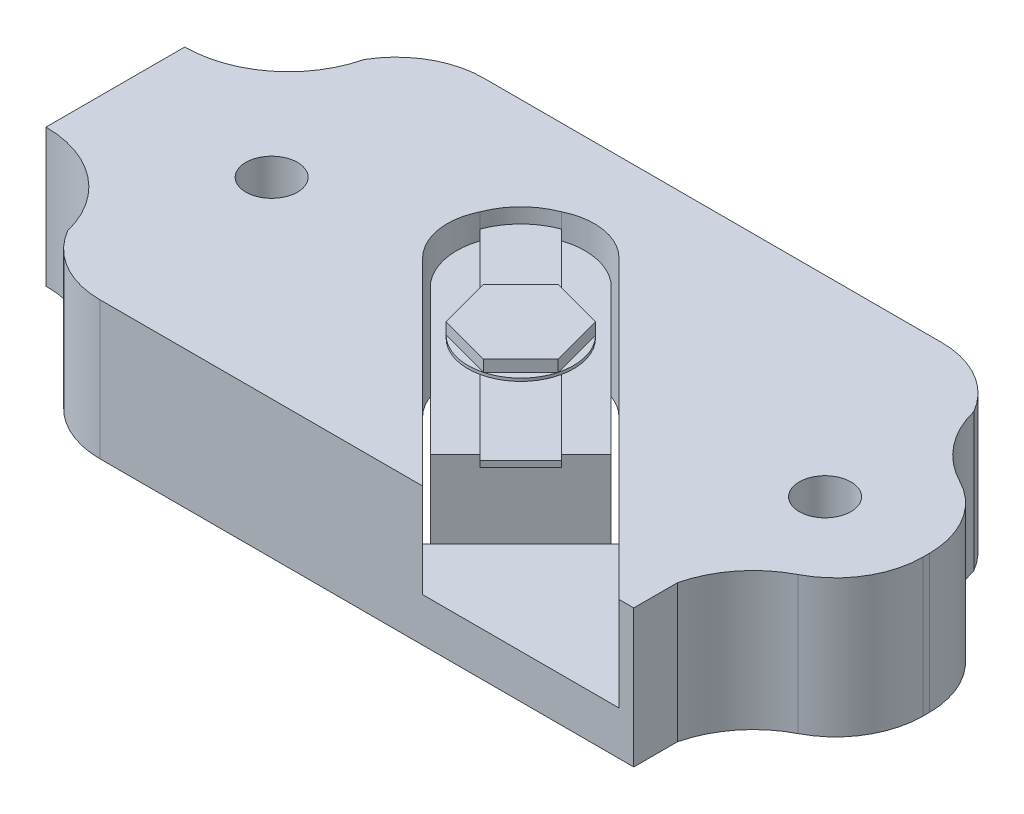
SolidWorks part; units mm, degrees
ref_plane "Front Plane" through (0, 0, 0) normal (0, 0, 1) x (1, 0, 0)
ref_plane "Top Plane" through (0, 0, 0) normal (0, 1, 0) x (1, 0, 0)
ref_plane "Right Plane" through (0, 0, 0) normal (1, 0, 0) x (0, 0, -1)
sketch "Sketch4" plane through (0, 0, 0) normal (0, 1, 0) x (1, 0, 0)
  line L0 (-37.15, 0) -> (37.15, 0) construction
  line L1 (37.15, 0) -> (28.55, 0) construction
  line L2 (37.15, 0) -> (-19.65, 0) construction
  circle A0 centre (-21.7, 0) radius 2.05
  circle A1 centre (26.5, 0) radius 2.05
  point P4 (0, 0)
  dimension "D4" = 4.1
  dimension "D5" = 4.1
  dimension "D6" = 2.05
  dimension "D1" = 74.3
  dimension "D2" = 8.6
  dimension "D3" = 56.8
sketch "Sketch1" plane through (0, 0, 0) normal (0, 1, 0) x (1, 0, 0)
  line L0 (-8.2731, 8.2731) -> (-4.7376, 4.7376) construction
  line L1 (-12.1976, 4.3487) -> (4.3487, -12.1976)
  line L2 (-12.1976, 4.3487) -> (-4.3487, 12.1976)
  line L3 (-4.3487, 12.1976) -> (12.1976, -4.3487)
  line L4 (4.3487, -12.1976) -> (12.1976, -4.3487)
  line L5 (-12.1976, 4.3487) -> (12.1976, -4.3487) construction
  line L6 (-4.3487, 12.1976) -> (4.3487, -12.1976) construction
  line L7 (-8.6621, 0.8132) -> (-0.8132, 8.6621) construction
  line L8 (0, 0) -> (-15.8275, 15.8275) construction
  line L9 (-37.15, 0) -> (37.15, 0) construction
  arc A0 (-8.6621, 0.8132) -> (-0.8132, 8.6621) centre (-4.3273, 4.3273) cw
  point P4 (0, 0)
  point P15 (-4.7376, 4.7376)
  point P16 (0, 0)
  dimension "D1" = 23.4
  dimension "D2" = 11.1
  dimension "D3" = 5
  dimension "D5" = 45
  dimension "D6" = 15.8275
extrude "Boss-Extrude1" add sketch "Sketch1" along normal blind 10.2 contours L1 L4 L3 region at (0.3923, 0, 0.3923)
sketch "Sketch2" plane through (0, 10.2, 0) normal (0, 1, 0) x (1, 0, 0)
  line L0 (8.2731, -8.2731) -> (-8.2731, 8.2731) construction
  line L1 (-0.8132, 8.6621) -> (12.1976, -4.3487) construction
  line L2 (-10.9955, 7.46) -> (7.46, -10.9955)
  line L3 (-8.6621, 0.8132) -> (4.3487, -12.1976)
  line L4 (4.3487, -12.1976) -> (12.1976, -4.3487)
  line L5 (12.1976, -4.3487) -> (-0.8132, 8.6621)
  line L6 (-8.6621, 0.8132) -> (4.3487, -12.1976)
  line L7 (4.3487, -12.1976) -> (12.1976, -4.3487)
  line L8 (12.1976, -4.3487) -> (-0.8132, 8.6621)
  line L9 (-10.9955, 7.46) -> (-7.46, 10.9955)
  line L10 (-7.46, 10.9955) -> (10.9955, -7.46)
  line L11 (7.46, -10.9955) -> (10.9955, -7.46)
  line L12 (-10.9955, 7.46) -> (10.9955, -7.46) construction
  line L13 (-7.46, 10.9955) -> (7.46, -10.9955) construction
  line L14 (3.2527, 3.2527) -> (-1.1906, 4.4433) construction
  line L15 (-1.1906, 4.4433) -> (-4.4433, 1.1906) construction
  line L16 (-4.4433, 1.1906) -> (-3.2527, -3.2527) construction
  line L17 (-3.2527, -3.2527) -> (1.1906, -4.4433) construction
  line L18 (1.1906, -4.4433) -> (4.4433, -1.1906) construction
  line L19 (4.4433, -1.1906) -> (3.2527, 3.2527) construction
  line L20 (-8.2731, 8.2731) -> (8.2731, -8.2731) construction
  circle A0 centre (0, 0) radius 3.9837 construction
  circle A3 centre (0, 0) radius 4.6 construction
  arc A4 (-0.8132, 8.6621) -> (-8.6621, 0.8132) centre (-4.3273, 4.3273) ccw
  arc A5 (-0.8132, 8.6621) -> (-8.6621, 0.8132) centre (-4.3273, 4.3273) ccw
  point P11 (0, 0)
  point P13 (0, 0)
  point P25 (0, 0)
  point P26 (0, 0)
  point P27 (-29.7928, -0.0293)
  line M18 (4.3487, -12.1976) -> (12.1976, -4.3487)
  dimension "D6" = 180
  dimension "D2" = 26.1
  dimension "D3" = 5
  dimension "D4" = 4.6
  dimension "D5" = 90
  dimension "D1" = 0
extrude "Boss-Extrude2" add sketch "Sketch2" along normal blind 0.5 contours L2 L11 L10 M18 | A3 L2 L10 M18 | A3 L10 L2 | L10 L9 L2 | L18 L19 L10 L14 L15 L16 L2 L17 | L15 A3 | L18 A3 region at (-8.6753, 10.2, -8.6753) region at (0.0677, 10.2, 0.0677) region at (8.7504, 10.2, 8.7504)
sketch "Sketch3" plane through (0, 10.7, 0) normal (0, 1, 0) x (1, 0, 0)
  line L0 (4.4433, -1.1906) -> (3.2527, 3.2527) construction
  line L1 (1.1906, -4.4433) -> (4.4433, -1.1906) construction
  line L2 (-3.2527, -3.2527) -> (1.1906, -4.4433) construction
  line L3 (-8.6621, 0.8132) -> (4.3487, -12.1976)
  line L4 (4.3487, -12.1976) -> (12.1976, -4.3487)
  line L5 (12.1976, -4.3487) -> (-0.8132, 8.6621)
  line L6 (-8.6621, 0.8132) -> (4.3487, -12.1976)
  line L7 (4.3487, -12.1976) -> (12.1976, -4.3487)
  line L8 (12.1976, -4.3487) -> (-0.8132, 8.6621)
  line L9 (-4.4433, 1.1906) -> (-3.2527, -3.2527) construction
  line L10 (-10.9955, 7.46) -> (7.46, -10.9955)
  line L11 (7.46, -10.9955) -> (10.9955, -7.46)
  line L12 (10.9955, -7.46) -> (-7.46, 10.9955)
  line L13 (-7.46, 10.9955) -> (-10.9955, 7.46)
  line L14 (-10.9955, 7.46) -> (7.46, -10.9955)
  line L15 (7.46, -10.9955) -> (10.9955, -7.46)
  line L16 (10.9955, -7.46) -> (-7.46, 10.9955)
  line L17 (-7.46, 10.9955) -> (-10.9955, 7.46)
  line L18 (-1.1906, 4.4433) -> (-4.4433, 1.1906) construction
  line L19 (3.2527, 3.2527) -> (-1.1906, 4.4433) construction
  line L20 (4.4433, -1.1906) -> (3.2527, 3.2527)
  line L21 (1.1906, -4.4433) -> (4.4433, -1.1906)
  line L22 (-3.2527, -3.2527) -> (1.1906, -4.4433)
  line L23 (-4.4433, 1.1906) -> (-3.2527, -3.2527)
  line L24 (-1.1906, 4.4433) -> (-4.4433, 1.1906)
  line L25 (3.2527, 3.2527) -> (-1.1906, 4.4433)
  circle A0 centre (0, 0) radius 3.9837 construction
  circle A3 centre (0, 0) radius 4.6 construction
  circle A4 centre (0, 0) radius 3.9837
  circle A5 centre (0, 0) radius 4.6
  arc A6 (-0.8132, 8.6621) -> (-8.6621, 0.8132) centre (-4.3273, 4.3273) ccw
  arc A7 (-0.8132, 8.6621) -> (-8.6621, 0.8132) centre (-4.3273, 4.3273) ccw
  line M24 (-10.9955, 7.46) -> (7.46, -10.9955)
  line M26 (10.9955, -7.46) -> (-7.46, 10.9955)
  dimension "D1" = 0
  dimension "D2" = 0
extrude "Boss-Extrude4" add sketch "Sketch3" along normal blind 0.25 separate body contours L21 A5 | L22 A5 L14 | A5 L23 M24 | L24 A5 | L25 A5 M26 | L16 A5 L20 | L14 A5 L22 | L23 A5 M24 | A5 L25 M26 | L20 A5 L16 region at (-4.4275, 10.7, -0.9867) region at (-4.0834, 10.7, 1.1201) region at (-1.1201, 10.7, 4.0834) region at (0.9867, 10.7, 4.4275) region at (-2.9923, 10.7, -2.9923) region at (1.1201, 10.7, -4.0834) region at (-0.9867, 10.7, -4.4275) region at (4.4275, 10.7, 0.9867) region at (4.0834, 10.7, -1.1201) region at (2.9923, 10.7, 2.9923)
extrude "Boss-Extrude5" add sketch "Sketch3<3>" along normal blind 1.25 contours A4 L20 L25 | A4 L16 L25 L24 | A4 M24 M26 | A4 M26 | L25 L24 L23 L22 L21 L20 region at (0, 10.7, 0) region at (-1.3125, 10.7, -3.9449) region at (2.9115, 10.7, -2.9115) region at (2.1949, 10.7, -2.1949)
sketch "Sketch3<3>" plane through (0, 10.7, 0) normal (0, 1, 0) x (1, 0, 0) same geometry as "Sketch3"
sketch "Sketch5" plane through (0, 0, 0) normal (0, 1, 0) x (1, 0, 0)
  line L0 (-9.0336, 0.4777) -> (4.3487, -12.9047)
  line L1 (4.3487, -12.9047) -> (12.9047, -4.3487)
  line L2 (12.9047, -4.3487) -> (-0.4777, 9.0336)
  line L3 (-8.6621, 0.8132) -> (4.3487, -12.1976)
  line L4 (-10.9955, 7.46) -> (7.46, -10.9955)
  line L5 (7.46, -10.9955) -> (10.9955, -7.46)
  line L6 (4.4433, -1.1906) -> (3.2527, 3.2527)
  line L7 (3.2527, 3.2527) -> (-1.1906, 4.4433)
  line L8 (-1.1906, 4.4433) -> (-4.4433, 1.1906)
  line L9 (-4.4433, 1.1906) -> (-3.2527, -3.2527)
  line L10 (-3.2527, -3.2527) -> (1.1906, -4.4433)
  line L11 (1.1906, -4.4433) -> (4.4433, -1.1906)
  line L12 (4.4433, -1.1906) -> (3.2527, 3.2527)
  line L13 (3.2527, 3.2527) -> (-1.1906, 4.4433)
  line L14 (-1.1906, 4.4433) -> (-4.4433, 1.1906)
  line L15 (-4.4433, 1.1906) -> (-3.2527, -3.2527)
  line L16 (-3.2527, -3.2527) -> (1.1906, -4.4433)
  line L17 (1.1906, -4.4433) -> (4.4433, -1.1906)
  line L18 (10.9955, -7.46) -> (-7.46, 10.9955)
  line L19 (-7.46, 10.9955) -> (-10.9955, 7.46)
  line L20 (-10.9955, 7.46) -> (7.46, -10.9955)
  line L21 (7.46, -10.9955) -> (10.9955, -7.46)
  line L22 (10.9955, -7.46) -> (-7.46, 10.9955)
  line L23 (-7.46, 10.9955) -> (-10.9955, 7.46)
  line L24 (4.3487, -12.1976) -> (12.1976, -4.3487)
  line L25 (12.1976, -4.3487) -> (-0.8132, 8.6621)
  line L26 (-8.6621, 0.8132) -> (4.3487, -12.1976)
  line L27 (4.3487, -12.1976) -> (12.1976, -4.3487)
  line L28 (12.1976, -4.3487) -> (-0.8132, 8.6621)
  line L29 (-37.15, 0) -> (37.15, 0) construction
  line L30 (-26.7, 12.9047) -> (31.5, 12.9047)
  line L31 (-26.7, 12.9047) -> (-26.7, -12.9047)
  line L32 (-26.7, -12.9047) -> (31.5, -12.9047)
  line L33 (31.5, 12.9047) -> (31.5, -12.9047)
  line L34 (-26.7, 12.9047) -> (31.5, -12.9047) construction
  line L35 (-26.7, -12.9047) -> (31.5, 12.9047) construction
  line L36 (-21.7, 7.62) -> (-21.7, -7.62) construction
  line L37 (-26.7, 7.62) -> (-20.7, 7.62) construction
  line L38 (-37.15, 0) -> (37.15, 0)
  line L39 (-26.7, -7.62) -> (-20.7, -7.62) construction
  line L40 (-30.51, -16.7147) -> (35.31, -16.7147)
  line L41 (35.31, 16.7147) -> (35.31, -16.7147)
  line L42 (-30.51, 16.7147) -> (35.31, 16.7147)
  line L43 (-30.51, 16.7147) -> (-30.51, -16.7147)
  line L44 (-23.75, 0) -> (-30.276, -1.5652) construction
  line L45 (0, 0) -> (0, -16.7147) construction
  line L46 (31.5, 6.0421) -> (35.31, 6.0421) construction
  line L47 (26.5517, 12.9047) -> (26.5517, 16.7147)
  line L48 (26.5517, -12.9047) -> (26.5517, -16.7147)
  line L49 (-26.5517, -12.9047) -> (-26.5517, -16.7147)
  line L50 (-26.5517, 12.9047) -> (-26.5517, 16.7147)
  line L51 (-35.31, 6.0421) -> (-35.31, -6.0421)
  line L52 (-9.0336, 0.4777) -> (-8.6621, 0.8132)
  line L53 (-0.8132, 8.6621) -> (-0.4777, 9.0336)
  arc A1 (-0.8132, 8.6621) -> (-8.6621, 0.8132) centre (-4.3273, 4.3273) ccw
  circle A3 centre (0, 0) radius 4.6
  circle A4 centre (0, 0) radius 4.6
  circle A5 centre (0, 0) radius 3.9837
  circle A6 centre (0, 0) radius 3.9837
  arc A7 (-0.4983, 9.0505) -> (-9.0505, 0.4983) centre (-4.3273, 4.3273) ccw
  arc A8 (-0.8132, 8.6621) -> (-8.6621, 0.8132) centre (-4.3273, 4.3273) ccw construction
  arc A9 (-0.8132, 8.6621) -> (-8.6621, 0.8132) centre (-4.3273, 4.3273) ccw
  arc A10 (-0.4777, 9.0336) -> (-9.0336, 0.4777) centre (-4.3273, 4.3273) ccw construction
  circle A11 centre (26.5, 0) radius 2.05 construction
  circle A12 centre (-21.7, 0) radius 2.05 construction
  circle A13 centre (26.5, 0) radius 2.05 construction
  circle A14 centre (-21.7, 0) radius 2.05 construction
  arc A15 (-17.6655, -12.9047) -> (-22.1527, -7.62) centre (-22.1527, -12.1673) ccw construction
  arc A17 (-22.1527, -7.62) -> (-30.51, 0) centre (-22.1526, 0.773) cw
  arc A18 (26.5517, 12.9047) -> (35.31, 6.0421) centre (35.31, 15.0622) ccw
  arc A19 (22.1527, 10.795) -> (33.6948, 0) centre (22.1526, -0.773) cw construction
  arc A20 (-22.1527, 7.62) -> (-30.51, 0) centre (-22.1526, -0.773) ccw construction
  arc A21 (26.5517, -12.9047) -> (35.31, -6.0421) centre (35.31, -15.0622) cw
  arc A22 (-26.5517, -12.9047) -> (-35.31, -6.0421) centre (-35.31, -15.0622) ccw
  arc A23 (22.1527, -7.62) -> (30.51, 0) centre (22.1526, 0.773) ccw construction
  arc A24 (22.1527, 7.62) -> (30.51, 0) centre (22.1526, -0.773) cw construction
  arc A25 (-26.5517, 12.9047) -> (-35.31, 6.0421) centre (-35.31, 15.0622) cw
  arc A28 (25.575, 10.2772) -> (31.5, 6.0421) centre (22.1526, -0.773) cw construction
  arc A29 (22.1527, -10.795) -> (33.6948, 0) centre (22.1526, 0.773) ccw construction
  point P30 (2.4, 0)
  point P43 (-21.7, 0)
  dimension "D7" = 0.5
  dimension "D12" = 4.5473
  dimension "D13" = 3.81
  dimension "D14" = 4.5473
  dimension "D15" = 7.05
  dimension "D17" = 3.175
  dimension "D18" = 8.393
  dimension "D19" = 9.0201
  dimension "D20" = 5.55
  dimension "D8" = 5
  dimension "D9" = 5
  dimension "D10" = 15.24
  dimension "D11" = 6
  dimension "D16" = 11.3395
  dimension "D1" = 0
  dimension "D2" = 0
  dimension "D3" = 0
  dimension "D4" = 0
  dimension "D5" = 0
  dimension "D6" = 0.5
extrude "Boss-Extrude6" add sketch "Sketch5" along normal blind 12 separate body contours L30 A25 L31 L38 L0 L52 A9 L20 L23 L22 L53 L2 L33 A18 | A22 L32 L0 L38 L31 | L32 A21 L33 L38 L2 L1 L22 L21 L20 | L33 A21 L41 L38 | A18 L33 L38 L41 | L50 L30 L47 L42 | L31 A25 L43 L38 | L43 A25 L51 L38 | A22 L43 L38 L51 | A22 L31 A17 L43 | A17 L31 L38 | L32 L49 L40 L48 | L21 L22 L1 L20 | A7 L22 L23 L20 region at (2.6529, 0, -6.7688) region at (-14.1181, 0, 7.0158) region at (0, 0, 14.8097) region at (19.784, 0, 6.425) region at (-28.4475, 0, -4.7416) region at (-28.2101, 0, 2.411) region at (8.9272, 0, 8.9272) region at (-28.6471, 0, 6.7003) region at (-32.8262, 0, 3.2568) region at (-32.8262, 0, -3.2568) region at (-8.8563, 0, -8.8563) region at (33.363, 0, 3.1639) region at (0, 0, -14.8097) region at (33.363, 0, -3.1639)
sketch "Sketch6" plane through (0, 12, 0) normal (0, 1, 0) x (1, 0, 0)
  line L0 (-8.6621, 0.8132) -> (4.3487, -12.1976) construction
  line L1 (4.3487, -12.1976) -> (12.1976, -4.3487) construction
  line L2 (12.1976, -4.3487) -> (-0.8132, 8.6621) construction
  line L3 (-0.8132, 8.6621) -> (-0.4777, 9.0336) construction
  line L4 (12.9047, -4.3487) -> (-0.4777, 9.0336) construction
  line L5 (4.3487, -12.9047) -> (12.9047, -4.3487) construction
  line L6 (-9.0336, 0.4777) -> (4.3487, -12.9047) construction
  line L7 (-9.0336, 0.4777) -> (-8.6621, 0.8132) construction
  line L8 (-37.15, 0) -> (37.15, 0) construction
  line L9 (26.5517, -12.9047) -> (26.5517, -16.7147) construction
  line L10 (26.5517, 12.9047) -> (26.5517, 16.7147) construction
  line L11 (-26.5517, 12.9047) -> (-26.5517, 16.7147) construction
  line L12 (-35.31, 6.0421) -> (-35.31, -6.0421) construction
  line L13 (-26.5517, -12.9047) -> (-26.5517, -16.7147) construction
  line L14 (-10.9955, 7.46) -> (7.46, -10.9955) construction
  line L15 (7.46, -10.9955) -> (10.9955, -7.46) construction
  line L16 (10.9955, -7.46) -> (-7.46, 10.9955) construction
  line L17 (-7.46, 10.9955) -> (-10.9955, 7.46) construction
  line L18 (4.4433, -1.1906) -> (3.2527, 3.2527) construction
  line L19 (3.2527, 3.2527) -> (-1.1906, 4.4433) construction
  line L20 (-1.1906, 4.4433) -> (-4.4433, 1.1906) construction
  line L21 (-4.4433, 1.1906) -> (-3.2527, -3.2527) construction
  line L22 (-3.2527, -3.2527) -> (1.1906, -4.4433) construction
  line L23 (1.1906, -4.4433) -> (4.4433, -1.1906) construction
  line L24 (-26.7, 12.9047) -> (31.5, 12.9047) construction
  line L25 (31.5, 12.9047) -> (31.5, -12.9047) construction
  line L26 (-26.7, -12.9047) -> (31.5, -12.9047) construction
  line L27 (-26.7, 12.9047) -> (-26.7, -12.9047) construction
  line L28 (-30.51, -16.7147) -> (35.31, -16.7147) construction
  line L29 (35.31, 16.7147) -> (35.31, -16.7147) construction
  line L30 (-30.51, 16.7147) -> (35.31, 16.7147) construction
  line L31 (-30.51, 16.7147) -> (-30.51, -16.7147) construction
  line L32 (-8.6621, 0.8132) -> (4.3487, -12.1976)
  line L33 (4.3487, -12.1976) -> (12.1976, -4.3487)
  line L34 (12.1976, -4.3487) -> (-0.8132, 8.6621)
  line L35 (-0.8132, 8.6621) -> (-0.4777, 9.0336)
  line L36 (12.9047, -4.3487) -> (-0.4777, 9.0336)
  line L37 (4.3487, -12.9047) -> (12.9047, -4.3487)
  line L38 (-9.0336, 0.4777) -> (4.3487, -12.9047)
  line L39 (-9.0336, 0.4777) -> (-8.6621, 0.8132)
  line L40 (-37.15, 0) -> (37.15, 0)
  line L41 (26.5517, -12.9047) -> (26.5517, -16.7147)
  line L42 (26.5517, 12.9047) -> (26.5517, 16.7147)
  line L43 (-26.5517, 12.9047) -> (-26.5517, 16.7147)
  line L44 (-35.31, 6.0421) -> (-35.31, -6.0421)
  line L45 (-26.5517, -12.9047) -> (-26.5517, -16.7147)
  line L46 (-10.9955, 7.46) -> (7.46, -10.9955)
  line L47 (7.46, -10.9955) -> (10.9955, -7.46)
  line L48 (10.9955, -7.46) -> (-7.46, 10.9955)
  line L49 (-7.46, 10.9955) -> (-10.9955, 7.46)
  line L50 (4.4433, -1.1906) -> (3.2527, 3.2527)
  line L51 (3.2527, 3.2527) -> (-1.1906, 4.4433)
  line L52 (-1.1906, 4.4433) -> (-4.4433, 1.1906)
  line L53 (-4.4433, 1.1906) -> (-3.2527, -3.2527)
  line L54 (-3.2527, -3.2527) -> (1.1906, -4.4433)
  line L55 (1.1906, -4.4433) -> (4.4433, -1.1906)
  line L56 (-26.7, 12.9047) -> (31.5, 12.9047)
  line L57 (31.5, 12.9047) -> (31.5, -12.9047)
  line L58 (-26.7, -12.9047) -> (31.5, -12.9047)
  line L59 (-26.7, 12.9047) -> (-26.7, -12.9047)
  line L60 (-30.51, -16.7147) -> (35.31, -16.7147)
  line L61 (35.31, 16.7147) -> (35.31, -16.7147)
  line L62 (-30.51, 16.7147) -> (35.31, 16.7147)
  line L63 (-30.51, 16.7147) -> (-30.51, -16.7147)
  line L64 (-10.0142, 6.4787) -> (-9.6228, 6.0872)
  arc A0 (-0.8132, 8.6621) -> (-8.6621, 0.8132) centre (-4.3273, 4.3273) ccw construction
  arc A1 (-0.4983, 9.0505) -> (-9.0505, 0.4983) centre (-4.3273, 4.3273) ccw construction
  arc A2 (-30.51, 0) -> (-22.1527, -7.62) centre (-22.1526, 0.773) ccw construction
  arc A3 (35.31, -6.0421) -> (26.5517, -12.9047) centre (35.31, -15.0622) ccw construction
  arc A4 (26.5517, 12.9047) -> (35.31, 6.0421) centre (35.31, 15.0622) ccw construction
  arc A5 (-35.31, 6.0421) -> (-26.5517, 12.9047) centre (-35.31, 15.0622) ccw construction
  arc A6 (-26.5517, -12.9047) -> (-35.31, -6.0421) centre (-35.31, -15.0622) ccw construction
  circle A7 centre (0, 0) radius 3.9837 construction
  circle A8 centre (0, 0) radius 4.6 construction
  arc A9 (-6.0872, 9.6228) -> (-9.6228, 6.0872) centre (-4.3273, 4.3273) ccw
  arc A10 (-6.4787, 10.0142) -> (-10.0142, 6.4787) centre (-4.3273, 4.3273) ccw
  arc A11 (-30.51, 0) -> (-22.1527, -7.62) centre (-22.1526, 0.773) ccw
  arc A12 (35.31, -6.0421) -> (26.5517, -12.9047) centre (35.31, -15.0622) ccw
  arc A13 (26.5517, 12.9047) -> (35.31, 6.0421) centre (35.31, 15.0622) ccw
  arc A14 (-35.31, 6.0421) -> (-26.5517, 12.9047) centre (-35.31, 15.0622) ccw
  arc A15 (-26.5517, -12.9047) -> (-35.31, -6.0421) centre (-35.31, -15.0622) ccw
  circle A16 centre (0, 0) radius 3.9837
  circle A17 centre (0, 0) radius 4.6
  arc A18 (-0.8132, 8.6621) -> (-6.0872, 9.6228) centre (-4.3273, 4.3273) ccw construction
  arc A19 (-9.6228, 6.0872) -> (-8.6621, 0.8132) centre (-4.3273, 4.3273) ccw construction
  arc A20 (-0.8132, 8.6621) -> (-6.0872, 9.6228) centre (-4.3273, 4.3273) ccw
  arc A21 (-9.6228, 6.0872) -> (-8.6621, 0.8132) centre (-4.3273, 4.3273) ccw
  arc A22 (-9.0336, 0.4777) -> (-10.0142, 6.4787) centre (-5.3513, 4.16) cw
  arc A23 (-0.4777, 9.0336) -> (-6.4787, 10.0142) centre (-4.16, 5.3513) ccw
  line M28 (-9.0336, 0.4777) -> (-8.6621, 0.8132)
  arc M29 (-8.6621, 0.8132) -> (-9.6228, 6.0872) centre (-4.3273, 4.3273) cw
  line M30 (-9.6228, 6.0872) -> (-10.0142, 6.4787)
  line M32 (-6.4787, 10.0142) -> (-6.0872, 9.6228)
  arc M33 (-6.0872, 9.6228) -> (-0.8132, 8.6621) centre (-4.3273, 4.3273) cw
  line M34 (-0.8132, 8.6621) -> (-0.4777, 9.0336)
extrude "Cut-Extrude1" cut sketch "Sketch6" against normal through all contours A22 M28 M29 M30 | A23 M34 M32 M33 region at (-9.9057, 12, -3.3769) region at (-3.3769, 12, -9.9057)
sketch "Sketch8" plane through (0, 12, 0) normal (0, 1, 0) x (1, 0, 0)
  line L0 (4.3487, -12.9047) -> (12.9047, -4.3487) construction
  line L1 (12.9047, -4.3487) -> (-0.4777, 9.0336) construction
  line L2 (-9.0336, 0.4777) -> (4.3487, -12.9047) construction
  line L3 (4.3487, -12.9047) -> (12.9047, -4.3487)
  line L4 (12.9047, -4.3487) -> (-0.4777, 9.0336)
  line L5 (-9.0336, 0.4777) -> (4.3487, -12.9047)
  line L6 (4.3487, -12.9047) -> (8.1587, -16.7147)
  line L7 (-26.5517, -16.7147) -> (26.5517, -16.7147) construction
  line L8 (12.9047, -4.3487) -> (25.2707, -16.7147)
  line L9 (25.2707, -16.7147) -> (8.1587, -16.7147)
  arc A0 (-6.4787, 10.0142) -> (-10.0142, 6.4787) centre (-4.3273, 4.3273) ccw construction
  arc A1 (-10.0142, 6.4787) -> (-9.0336, 0.4777) centre (-5.3513, 4.16) ccw construction
  arc A2 (-0.4777, 9.0336) -> (-6.4787, 10.0142) centre (-4.16, 5.3513) ccw construction
  arc A3 (-6.4787, 10.0142) -> (-10.0142, 6.4787) centre (-4.3273, 4.3273) ccw
  arc A4 (-10.0142, 6.4787) -> (-9.0336, 0.4777) centre (-5.3513, 4.16) ccw
  arc A5 (-0.4777, 9.0336) -> (-6.4787, 10.0142) centre (-4.16, 5.3513) ccw
  line M10 (-26.5517, -16.7147) -> (26.5517, -16.7147)
  line M24 (12.9047, -4.3487) -> (4.3487, -12.9047)
extrude "Cut-Extrude2" cut sketch "Sketch8" against normal offset from surface (8.19 mm away) 3.81 contours L8 L6 M24 M10 region at (13.8021, 12, 12.2936) up to face at (0, 0, 0)
sketch "Sketch9" plane through (0, 0, 0) normal (0, -1, 0) x (-1, 0, 0)
  point P0 (-26.5, 0)
  point P3 (21.7, 0)
hole_wizard "M4 Clearance Hole1" positions "Sketch9" profile "Sketch10" hole size "M4" standard "ANSI Metric" end condition through all
sketch "Sketch10" plane through (26.5, 0, 0) normal (1, 0, 0) x (0, 0, -1)
  line L0 (0, 0) -> (0, 12)
  line L1 (0, 12) -> (2.25, 12)
  line L2 (2.25, 12) -> (2.25, 0)
  line L5 (2.25, 0) -> (0, 0)
  line L11 (0, -6.35) -> (0, 107.95) construction
  dimension "Thru Hole Dia." = 4.5
  dimension "Thru Hole Depth" = 12
fillet "Fillet1" radius 7.62 2 edges at (35.31, 6, -6.0421) (35.31, 6, 6.0421)
fillet "Fillet2" radius 7.62 3 edges at (-26.5517, 6, 16.7147) (-26.5517, 6, -16.7147) (26.5517, 6, -16.7147)
